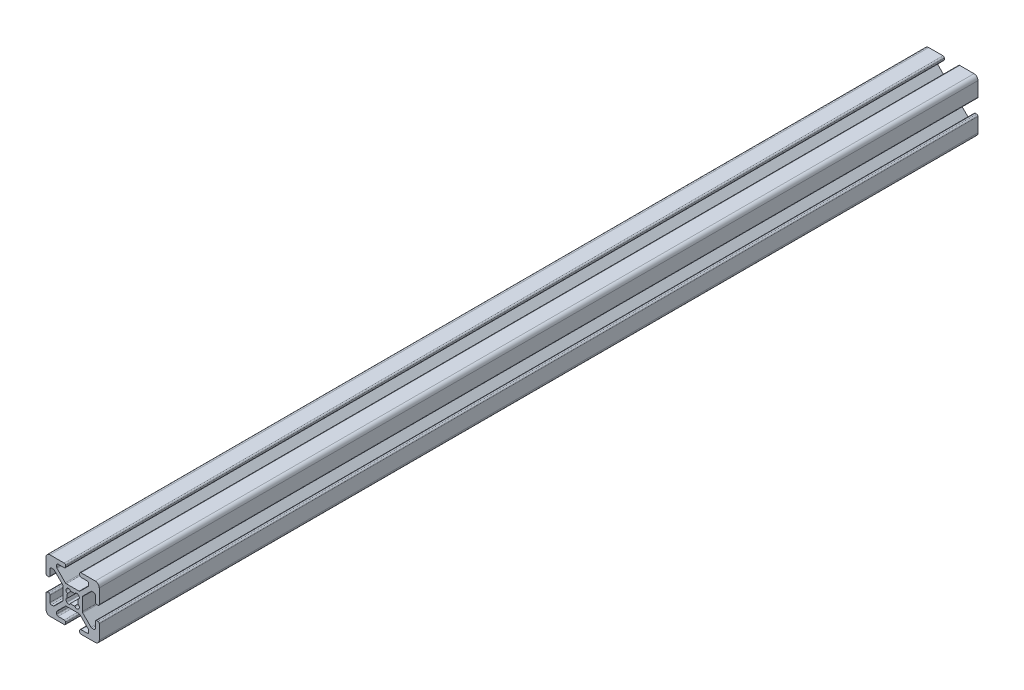
SolidWorks part; units mm, degrees
material "6105-T5 Aluminum"
ref_plane "Front Plane" through (0, 0, 0) normal (0, 0, 1) x (1, 0, 0)
ref_plane "Top Plane" through (0, 0, 0) normal (0, 1, 0) x (1, 0, 0)
ref_plane "Right Plane" through (0, 0, 0) normal (1, 0, 0) x (0, 0, -1)
sketch "Sketch1" plane through (0, 0, 0) normal (0, 0, 1) x (1, 0, 0)
  line L0 (9.492, 2.63) -> (9.008, 2.63)
  line L1 (8.5, 3.138) -> (8.5, 5.487)
  line L2 (10, 3.138) -> (10, 8.5)
  line L3 (3.655, -2.3839) -> (3.655, 2.3839)
  line L4 (7.2661, 5.995) -> (7.992, 5.995)
  line L5 (6.9069, 5.8462) -> (3.8038, 2.7431)
  line L6 (9.492, -2.63) -> (9.008, -2.63)
  line L7 (10, -3.138) -> (10, -8.5)
  line L8 (8.5, -3.138) -> (8.5, -5.487)
  line L9 (7.2661, -5.995) -> (7.992, -5.995)
  line L10 (6.9069, -5.8462) -> (3.8038, -2.7431)
  line L11 (2.1249, -2.3045) -> (2.3045, -2.1249)
  line L12 (-2.63, 9.492) -> (-2.63, 9.008)
  line L13 (-3.138, 10) -> (-8.5, 10)
  line L14 (-3.138, 8.5) -> (-5.487, 8.5)
  line L15 (2.3839, 3.655) -> (-2.3839, 3.655)
  line L16 (-5.995, 7.2661) -> (-5.995, 7.992)
  line L17 (-5.8462, 6.9069) -> (-2.7431, 3.8038)
  line L18 (2.63, 9.492) -> (2.63, 9.008)
  line L19 (3.138, 10) -> (8.5, 10)
  line L20 (3.138, 8.5) -> (5.487, 8.5)
  line L21 (5.995, 7.2661) -> (5.995, 7.992)
  line L22 (5.8462, 6.9069) -> (2.7431, 3.8038)
  line L23 (2.3045, 2.1249) -> (2.1249, 2.3045)
  line L24 (-9.492, -2.63) -> (-9.008, -2.63)
  line L25 (-10, -3.138) -> (-10, -8.5)
  line L26 (-8.5, -3.138) -> (-8.5, -5.487)
  line L27 (-3.655, 2.3839) -> (-3.655, -2.3839)
  line L28 (-7.2661, -5.995) -> (-7.992, -5.995)
  line L29 (-6.9069, -5.8462) -> (-3.8038, -2.7431)
  line L30 (-9.492, 2.63) -> (-9.008, 2.63)
  line L31 (-10, 3.138) -> (-10, 8.5)
  line L32 (-8.5, 3.138) -> (-8.5, 5.487)
  line L33 (-7.2661, 5.995) -> (-7.992, 5.995)
  line L34 (-6.9069, 5.8462) -> (-3.8038, 2.7431)
  line L35 (-2.1249, 2.3045) -> (-2.3045, 2.1249)
  line L36 (2.63, -9.492) -> (2.63, -9.008)
  line L37 (3.138, -10) -> (8.5, -10)
  line L38 (3.138, -8.5) -> (5.487, -8.5)
  line L39 (-2.3839, -3.655) -> (2.3839, -3.655)
  line L40 (5.995, -7.2661) -> (5.995, -7.992)
  line L41 (5.8462, -6.9069) -> (2.7431, -3.8038)
  line L42 (-2.63, -9.492) -> (-2.63, -9.008)
  line L43 (-3.138, -10) -> (-8.5, -10)
  line L44 (-3.138, -8.5) -> (-5.487, -8.5)
  line L45 (-5.995, -7.2661) -> (-5.995, -7.992)
  line L46 (-5.8462, -6.9069) -> (-2.7431, -3.8038)
  line L47 (-2.3045, -2.1249) -> (-2.1249, -2.3045)
  arc A0 (-0.804, -1.9351) -> (0.804, -1.9351) centre (0, 0) ccw
  arc A1 (8.5, 5.487) -> (7.992, 5.995) centre (7.992, 5.487) ccw
  arc A2 (7.2661, 5.995) -> (6.9069, 5.8462) centre (7.2661, 5.487) ccw
  arc A3 (3.8038, 2.7431) -> (3.655, 2.3839) centre (4.163, 2.3839) ccw
  arc A4 (3.655, -2.3839) -> (3.8038, -2.7431) centre (4.163, -2.3839) ccw
  arc A5 (6.9069, -5.8462) -> (7.2661, -5.995) centre (7.2661, -5.487) ccw
  arc A6 (7.992, -5.995) -> (8.5, -5.487) centre (7.992, -5.487) ccw
  arc A7 (9.008, -2.63) -> (8.5, -3.138) centre (9.008, -3.138) ccw
  arc A8 (10, -3.138) -> (9.492, -2.63) centre (9.492, -3.138) ccw
  arc A9 (9.492, 2.63) -> (10, 3.138) centre (9.492, 3.138) ccw
  arc A10 (8.5, 3.138) -> (9.008, 2.63) centre (9.008, 3.138) ccw
  arc A11 (0.804, -1.9351) -> (2.1249, -2.3045) centre (1.5684, -1.748) ccw
  arc A12 (2.3045, -2.1249) -> (1.9351, -0.804) centre (1.748, -1.5684) ccw
  arc A13 (-2.63, 9.492) -> (-3.138, 10) centre (-3.138, 9.492) ccw
  arc A14 (-3.138, 8.5) -> (-2.63, 9.008) centre (-3.138, 9.008) ccw
  arc A15 (1.9351, -0.804) -> (1.9351, 0.804) centre (0, 0) ccw
  arc A16 (-2.7431, 3.8038) -> (-2.3839, 3.655) centre (-2.3839, 4.163) ccw
  arc A17 (-5.487, 8.5) -> (-5.995, 7.992) centre (-5.487, 7.992) ccw
  arc A18 (-5.995, 7.2661) -> (-5.8462, 6.9069) centre (-5.487, 7.2661) ccw
  arc A19 (2.63, 9.008) -> (3.138, 8.5) centre (3.138, 9.008) ccw
  arc A20 (3.138, 10) -> (2.63, 9.492) centre (3.138, 9.492) ccw
  arc A21 (5.995, 7.992) -> (5.487, 8.5) centre (5.487, 7.992) ccw
  arc A22 (5.8462, 6.9069) -> (5.995, 7.2661) centre (5.487, 7.2661) ccw
  arc A23 (2.3839, 3.655) -> (2.7431, 3.8038) centre (2.3839, 4.163) ccw
  arc A24 (1.9351, 0.804) -> (2.3045, 2.1249) centre (1.748, 1.5684) ccw
  arc A25 (2.1249, 2.3045) -> (0.804, 1.9351) centre (1.5684, 1.748) ccw
  arc A26 (-9.492, -2.63) -> (-10, -3.138) centre (-9.492, -3.138) ccw
  arc A27 (-8.5, -3.138) -> (-9.008, -2.63) centre (-9.008, -3.138) ccw
  arc A28 (0.804, 1.9351) -> (-0.804, 1.9351) centre (0, 0) ccw
  arc A29 (-3.8038, -2.7431) -> (-3.655, -2.3839) centre (-4.163, -2.3839) ccw
  arc A30 (-8.5, -5.487) -> (-7.992, -5.995) centre (-7.992, -5.487) ccw
  arc A31 (-7.2661, -5.995) -> (-6.9069, -5.8462) centre (-7.2661, -5.487) ccw
  arc A32 (-9.008, 2.63) -> (-8.5, 3.138) centre (-9.008, 3.138) ccw
  arc A33 (-10, 3.138) -> (-9.492, 2.63) centre (-9.492, 3.138) ccw
  arc A34 (-7.992, 5.995) -> (-8.5, 5.487) centre (-7.992, 5.487) ccw
  arc A35 (-6.9069, 5.8462) -> (-7.2661, 5.995) centre (-7.2661, 5.487) ccw
  arc A36 (-3.655, 2.3839) -> (-3.8038, 2.7431) centre (-4.163, 2.3839) ccw
  arc A37 (-0.804, 1.9351) -> (-2.1249, 2.3045) centre (-1.5684, 1.748) ccw
  arc A38 (-2.3045, 2.1249) -> (-1.9351, 0.804) centre (-1.748, 1.5684) ccw
  arc A39 (2.63, -9.492) -> (3.138, -10) centre (3.138, -9.492) ccw
  arc A40 (3.138, -8.5) -> (2.63, -9.008) centre (3.138, -9.008) ccw
  arc A41 (-1.9351, 0.804) -> (-1.9351, -0.804) centre (0, 0) ccw
  arc A42 (2.7431, -3.8038) -> (2.3839, -3.655) centre (2.3839, -4.163) ccw
  arc A43 (5.487, -8.5) -> (5.995, -7.992) centre (5.487, -7.992) ccw
  arc A44 (5.995, -7.2661) -> (5.8462, -6.9069) centre (5.487, -7.2661) ccw
  arc A45 (-2.63, -9.008) -> (-3.138, -8.5) centre (-3.138, -9.008) ccw
  arc A46 (-3.138, -10) -> (-2.63, -9.492) centre (-3.138, -9.492) ccw
  arc A47 (-5.995, -7.992) -> (-5.487, -8.5) centre (-5.487, -7.992) ccw
  arc A48 (-5.8462, -6.9069) -> (-5.995, -7.2661) centre (-5.487, -7.2661) ccw
  arc A49 (-2.3839, -3.655) -> (-2.7431, -3.8038) centre (-2.3839, -4.163) ccw
  arc A50 (-1.9351, -0.804) -> (-2.3045, -2.1249) centre (-1.748, -1.5684) ccw
  arc A51 (-2.1249, -2.3045) -> (-0.804, -1.9351) centre (-1.5684, -1.748) ccw
  arc A52 (10, 8.5) -> (8.5, 10) centre (8.5, 8.5) ccw
  arc A53 (8.5, -10) -> (10, -8.5) centre (8.5, -8.5) ccw
  arc A54 (-10, -8.5) -> (-8.5, -10) centre (-8.5, -8.5) ccw
  arc A55 (-8.5, 10) -> (-10, 8.5) centre (-8.5, 8.5) ccw
extrude "Extrude1" add sketch "Sketch1" against normal blind 330
